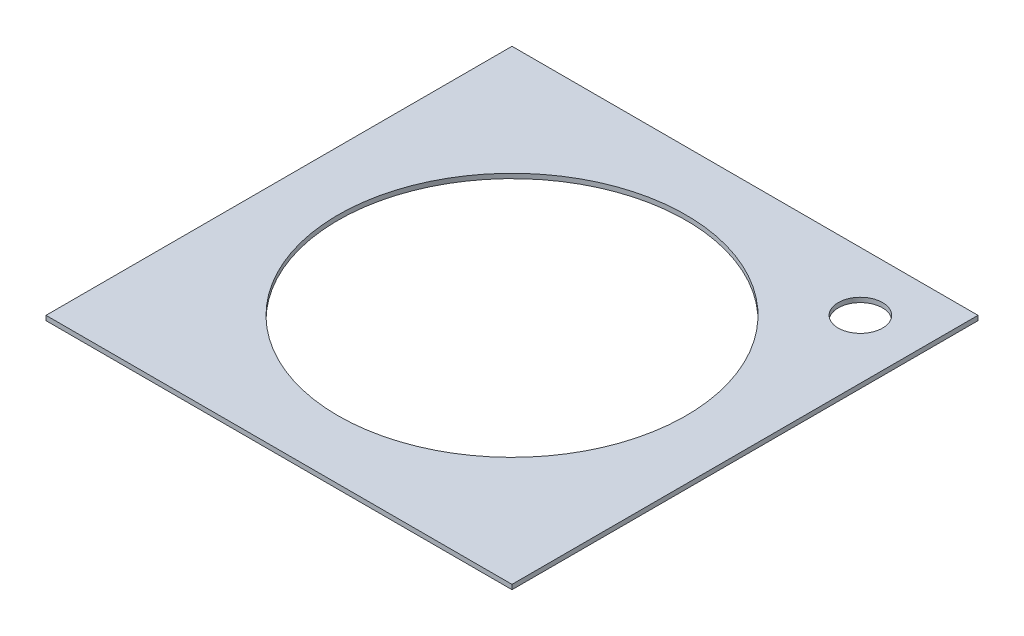
SolidWorks part; units mm, degrees
ref_plane "Front Plane" through (0, 0, 0) normal (0, 0, 1) x (1, 0, 0)
ref_plane "Top Plane" through (0, 0, 0) normal (0, 1, 0) x (1, 0, 0)
ref_plane "Right Plane" through (0, 0, 0) normal (1, 0, 0) x (0, 0, -1)
sketch "Sketch1" plane through (0, 0, 0) normal (0, 1, 0) x (1, 0, 0)
  line L1 (0, 0) -> (300, 0)
  line L2 (0, 0) -> (0, -300)
  line L3 (0, -300) -> (300, -300)
  line L4 (300, 0) -> (300, -300)
  dimension "D1" = 300
  dimension "D2" = 300
extrude "Boss-Extrude1" add sketch "Sketch1" along normal blind 3
sketch "Sketch2" plane through (0, 3, 0) normal (0, 1, 0) x (1, 0, 0)
  line L0 (300, -300) -> (300, 0) construction
  line L1 (0, -300) -> (300, -300) construction
  line L2 (150, -150) -> (300, 0) construction
  circle A0 centre (150, -150) radius 112
  circle A1 centre (262.1471, -37.8529) radius 14.255
  point P2 (0, 0)
  point P5 (300, -150)
  point P8 (150, -300)
  dimension "D1" = 224
  dimension "D3" = 28.51
  dimension "D2" = 158.6
extrude "Cut-Extrude1" cut sketch "Sketch2" against normal up to next
